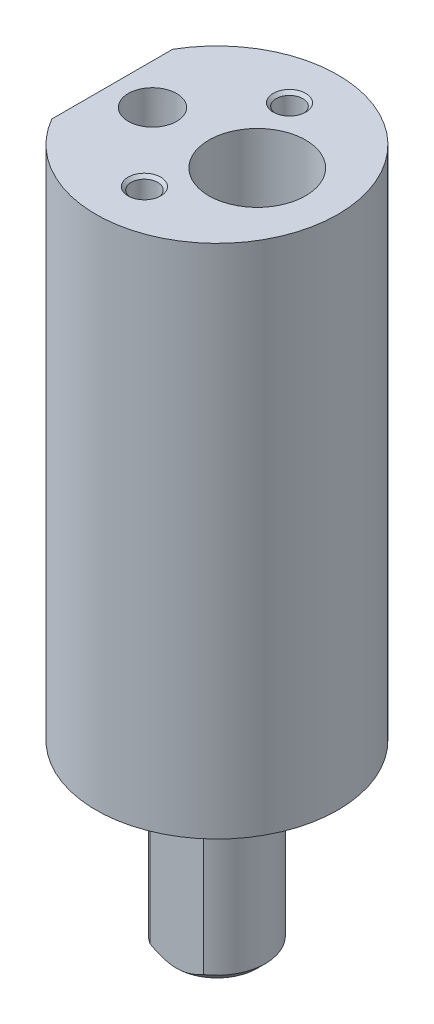
SolidWorks part; units mm, degrees
ref_plane "Front Plane" through (0, 0, 0) normal (0, 0, 1) x (1, 0, 0)
ref_plane "Top Plane" through (0, 0, 0) normal (0, 1, 0) x (1, 0, 0)
ref_plane "Right Plane" through (0, 0, 0) normal (1, 0, 0) x (0, 0, -1)
sketch "Sketch1" plane through (0, 0, 0) normal (0, 1, 0) x (1, 0, 0)
  line L0 (-3.3166, -5) -> (3.3166, -5)
  arc A0 (3.3166, -5) -> (-3.3166, -5) centre (0, 0) ccw
  dimension "D1" = 12
  dimension "D2" = 5
extrude "Boss-Extrude1" add sketch "Sketch1" along normal blind 22
sketch "Sketch2" plane through (0, 22, 0) normal (0, 1, 0) x (1, 0, 0)
  line L0 (-13, 7.4833) -> (-13, -7.4833)
  arc A0 (-13, -7.4833) -> (-13, 7.4833) centre (0, 0) ccw
  dimension "D1" = 30
  dimension "D2" = 13
extrude "Boss-Extrude2" add sketch "Sketch2" along normal blind 64
sketch "Sketch3" plane through (0, 86, 0) normal (0, 1, 0) x (1, 0, 0)
  line L0 (0, 0) -> (-13, 0) construction
  line L1 (-13, 7.4833) -> (-13, -7.4833) construction
  circle A0 centre (-8, 0) radius 3
  dimension "D2" = 6
  dimension "D1" = 8
extrude "Cut-Extrude1" cut sketch "Sketch3" against normal blind 65
sketch "Sketch4" plane through (0, 86, 0) normal (0, 1, 0) x (1, 0, 0)
  circle A0 centre (5, 0) radius 6
  dimension "D1" = 5
  dimension "D2" = 12
extrude "Cut-Extrude2" cut sketch "Sketch4" against normal blind 52
hole_wizard "M4 Tapped Hole1" positions "Sketch5" profile "Sketch6" tap size "M4" standard "ISO"
sketch "Sketch5" plane through (0, 86, 0) normal (0, 1, 0) x (1, 0, 0)
  line L0 (0, 9) -> (0, -9) construction
  point P1 (0, 9)
  point P2 (0, -9)
  dimension "D1" = 9
  dimension "D2" = 9
sketch "Sketch6" plane through (0, 86, -9) normal (1, 0, 0) x (0, 0, 1)
  line L0 (0, 0) -> (0, 14.9914)
  line L1 (0, 14.9914) -> (1.65, 14)
  line L2 (1.65, 14) -> (1.65, 0.375)
  line L3 (1.65, 0.375) -> (2.025, 0)
  line L5 (2.025, 0) -> (0, 0)
  line L6 (-1.65, 0.375) -> (-2.025, 0) construction
  line L10 (0, 14.9914) -> (-1.65, 14) construction
  line L11 (0, -6.35) -> (0, 107.95) construction
  dimension "Tap Drill Dia." = 3.3
  dimension "Tap Drill Depth" = 14
  dimension "Near C'Sink Dia." = 4.05
  dimension "Near C'Sink Angle" = 90
  dimension "Drill Angle" = 118
cosmetic thread "Hole Thread1" parameters "D1"=13.3, "D2"=4
cosmetic thread "Hole Thread2" parameters "D1"=13.3, "D2"=4
sketch "Sketch7" plane through (-13, 0, 0) normal (-1, 0, 0) x (0, 0, 1)
  line L0 (0, 86) -> (0, 22) construction
  line L1 (-7.4833, 86) -> (7.4833, 86) construction
  line L2 (-7.4833, 22) -> (7.4833, 22) construction
  circle A0 centre (0, 54) radius 2.5
  circle A1 centre (0, 25) radius 1.5
  dimension "D1" = 5
  dimension "D2" = 3
  dimension "D3" = 32
  dimension "D4" = 61
extrude "Cut-Extrude3" cut sketch "Sketch7" against normal blind 5
sketch "Sketch8" plane through (-13, 0, 0) normal (-1, 0, 0) x (0, 0, 1)
  line L0 (0, 86) -> (0, 22) construction
  line L1 (-7.4833, 86) -> (7.4833, 86) construction
  line L2 (-7.4833, 22) -> (7.4833, 22) construction
  circle A0 centre (0, 76) radius 1
  circle A1 centre (0, 34) radius 1
  dimension "D3" = 2
  dimension "D1" = 10
  dimension "D2" = 52
extrude "Cut-Extrude4" cut sketch "Sketch8" against normal blind 15
chamfer "Chamfer1" distance 1 angle 45 1 edges at (0, 0, -6)
